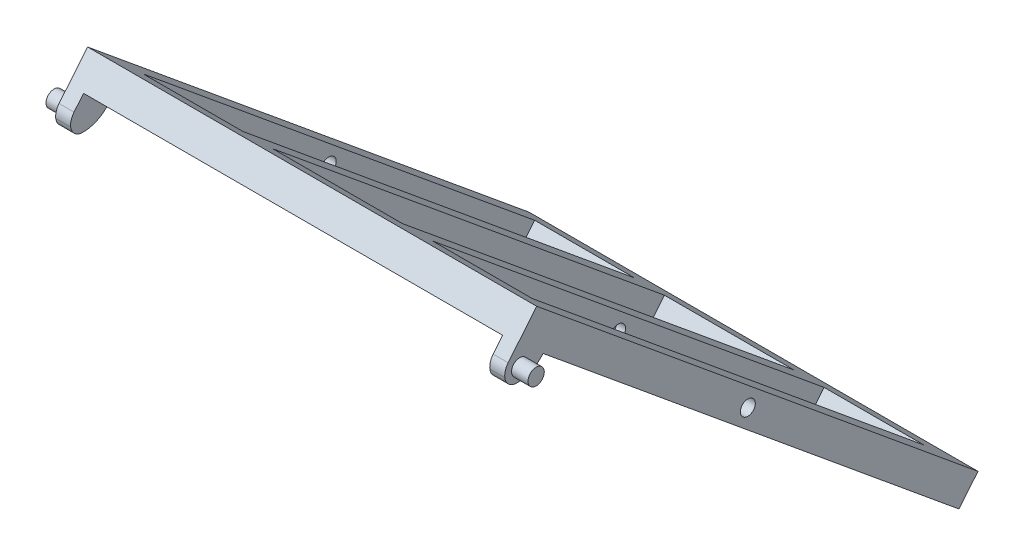
SolidWorks part; units mm, degrees
material "Acero al carbono no aleado"
ref_plane "Alzado" through (0, 0, 0) normal (0, 0, 1) x (1, 0, 0)
ref_plane "Planta" through (0, 0, 0) normal (0, 1, 0) x (1, 0, 0)
ref_plane "Vista lateral" through (0, 0, 0) normal (1, 0, 0) x (0, 0, -1)
ref_plane "Plano1" through (0, -1955.2536, 1610.9898) normal (0, 0.7718, -0.6359) x (1, 0, 0)
sketch "Croquis1" plane through (0, -1955.2536, 1610.9898) normal (0, 0.7718, -0.6359) x (1, 0, 0)
  line L0 (-255.3327, -2855.3915) -> (-255.3327, -1155.3915) construction
  line L1 (-1655.3327, -1155.3915) -> (-155.3327, -1155.3915)
  line L2 (-1655.3327, -1155.3915) -> (-1655.3327, -3065.3915)
  line L3 (-1655.3327, -3065.3915) -> (-155.3327, -3065.3915)
  line L4 (-155.3327, -1155.3915) -> (-155.3327, -3065.3915)
  line L5 (-1555.3327, -2955.3915) -> (-255.3327, -2955.3915)
  line L6 (-1555.3327, -2955.3915) -> (-1555.3327, -1259.8901)
  line L7 (-1555.3327, -1259.8901) -> (-255.3327, -1259.8901)
  line L8 (-255.3327, -2955.3915) -> (-255.3327, -1259.8901)
  dimension "D1" = 104.4986
extrude "Saliente-Extruir1" add sketch "Croquis1" along normal blind 100
sketch "Croquis2" plane through (0, 1949.2546, 2365.8046) normal (0, 0.6359, 0.7718) x (1, 0, 0)
  line L0 (-1655.3327, -2633.4373) -> (-1555.3327, -2633.4373) construction
  line L1 (-1655.3327, -2533.4373) -> (-1605.3327, -2533.4373)
  line L2 (-1655.3327, -2533.4373) -> (-1655.3327, -2633.4373)
  line L3 (-1655.3327, -2633.4373) -> (-1605.3327, -2633.4373)
  line L4 (-1605.3327, -2533.4373) -> (-1605.3327, -2633.4373)
  dimension "D1" = 50
extrude "Saliente-Extruir2" add sketch "Croquis2" against normal up to surface (110 mm away)
sketch "Croquis3" plane through (-1655.3327, 0, 0) normal (-1, 0, 0) x (0, 0, 1)
  circle A0 centre (3970, -76.3825) radius 27.1845
  dimension "D1" = 54.369
extrude "Saliente-Extruir3" add sketch "Croquis3" along normal blind 55
fillet "Redondeo1" radius 50 1 edges at (-1630.3327, -83.1769, 4040.3835)
fillet "Redondeo2" radius 110 1 edges at (-1630.3327, -153.1249, 3955.4878)
fillet "Redondeo3" radius 40 1 edges at (-1630.3327, -114.9715, 4001.7945)
ref_plane "Plano2" through (-905.3327, 0, 0) normal (1, 0, 0) x (0, 0, -1)
mirror "Simetría6" about plane through (-905.3327, 0, 0) normal (1, 0, 0) of "Redondeo3", "Redondeo2", "Redondeo1", "Saliente-Extruir3", "Saliente-Extruir2"
sketch "Croquis4" plane through (0, -1878.0757, 1547.4007) normal (0, 0.7718, -0.6359) x (1, 0, 0)
  line L0 (-1555.3327, -2955.3915) -> (-255.3327, -2955.3915) construction
  line L1 (-1222.0327, -2955.3915) -> (-1122.0327, -2955.3915)
  line L2 (-1222.0327, -2955.3915) -> (-1222.0327, -1259.8901)
  line L3 (-1222.0327, -1259.8901) -> (-1122.0327, -1259.8901)
  line L4 (-1122.0327, -2955.3915) -> (-1122.0327, -1259.8901)
  line L5 (-255.3327, -1259.8901) -> (-1555.3327, -1259.8901) construction
  line L6 (-905.3327, -2955.3915) -> (-905.3327, -1259.8901) construction
  line L8 (-1555.3327, -1259.8901) -> (-1555.3327, -2955.3915) construction
  line L9 (-588.6327, -1259.8901) -> (-688.6327, -1259.8901)
  line L10 (-588.6327, -2955.3915) -> (-688.6327, -2955.3915)
  line L11 (-588.6327, -2955.3915) -> (-588.6327, -1259.8901)
  line L12 (-688.6327, -2955.3915) -> (-688.6327, -1259.8901)
  dimension "D1" = 100
  dimension "D2" = 333.3
extrude "Saliente-Extruir4" add sketch "Croquis4" against normal up to surface (100 mm away) up to face at (-905.3327, -615.024, 3237.6226)
sketch "Croquis5" plane through (-588.6327, 0, 0) normal (1, 0, 0) x (0, 0, -1)
  line L0 (-3828.3096, 1.2309) -> (-2519.7573, -1076.9231) construction
  line L2 (-3913.2053, 71.1789) -> (-4008.5889, -44.588) construction
  circle A0 centre (-3207.951, -574.6859) radius 25
  dimension "D3" = 50
  dimension "D1" = 50
  dimension "D2" = 955
extrude "Cortar-Extruir1" cut sketch "Croquis5" against normal blind 30
sketch "Croquis6" plane through (-255.3327, 0, 0) normal (-1, 0, 0) x (0, 0, 1)
  line L0 (3828.3096, 1.2309) -> (2519.7573, -1076.9231) construction
  line L1 (3913.2053, 71.1789) -> (4008.5889, -44.588) construction
  circle A0 centre (3207.951, -574.6859) radius 25
  dimension "D3" = 50
  dimension "D1" = 50
  dimension "D2" = 955
extrude "Cortar-Extruir3" cut sketch "Croquis6" against normal through all
mirror "Simetría11" about plane through (-905.3327, 0, 0) normal (1, 0, 0) of "Cortar-Extruir1", "Cortar-Extruir3"
